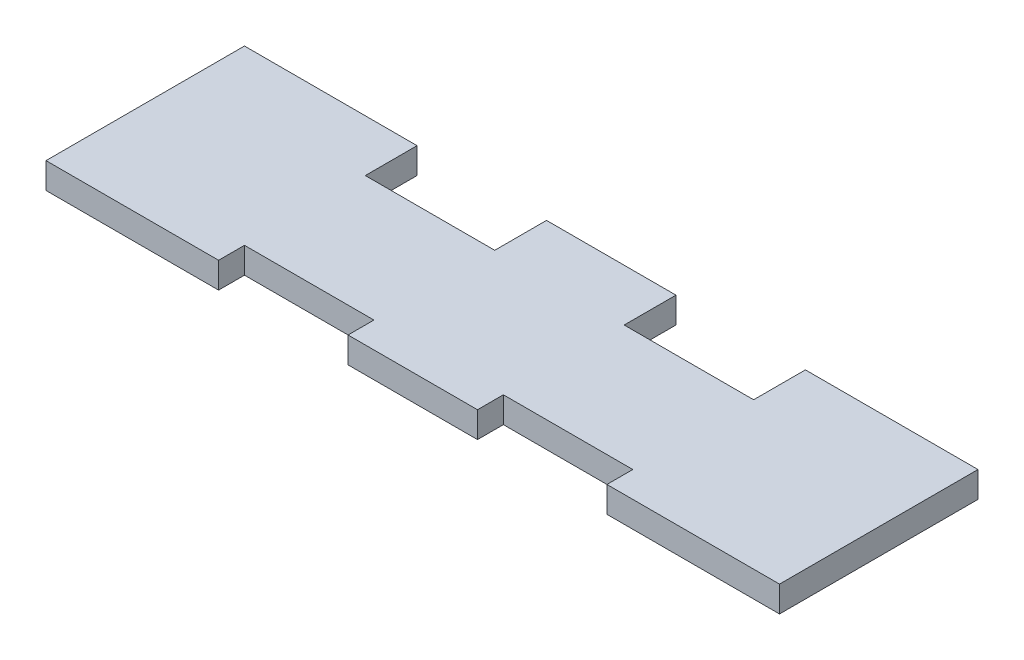
SolidWorks part; units mm, degrees
ref_plane "Alzado" through (0, 0, 0) normal (0, 0, 1) x (1, 0, 0)
ref_plane "Planta" through (0, 0, 0) normal (0, 1, 0) x (1, 0, 0)
ref_plane "Vista lateral" through (0, 0, 0) normal (1, 0, 0) x (0, 0, -1)
sketch "Croquis1" plane through (0, 0, 0) normal (0, 1, 0) x (1, 0, 0)
  line L0 (0, 0) -> (20, 0)
  line L1 (20, 0) -> (20, 3)
  line L2 (20, 3) -> (35, 3)
  line L3 (35, 3) -> (35, 0)
  line L4 (35, 0) -> (50, 0)
  line L6 (85, 0) -> (65, 0)
  line L7 (50, 3) -> (50, 0)
  line L8 (65, 3) -> (50, 3)
  line L9 (65, 0) -> (65, 3)
  line L10 (0, 0) -> (0, 23)
  line L11 (0, 23) -> (20, 23)
  line L12 (20, 23) -> (20, 17)
  line L13 (20, 17) -> (35, 17)
  line L14 (35, 17) -> (35, 23)
  line L15 (35, 23) -> (50, 23)
  line L16 (50, 23) -> (50, 17)
  line L17 (50, 17) -> (65, 17)
  line L18 (65, 17) -> (65, 23)
  line L19 (65, 23) -> (85, 23)
  line L20 (85, 23) -> (85, 0)
  dimension "D1" = 20
  dimension "D2" = 3
  dimension "D3" = 15
  dimension "D4" = 15
  dimension "D5" = 23
  dimension "D6" = 6
extrude "Saliente-Extruir1" add sketch "Croquis1" along normal blind 3
